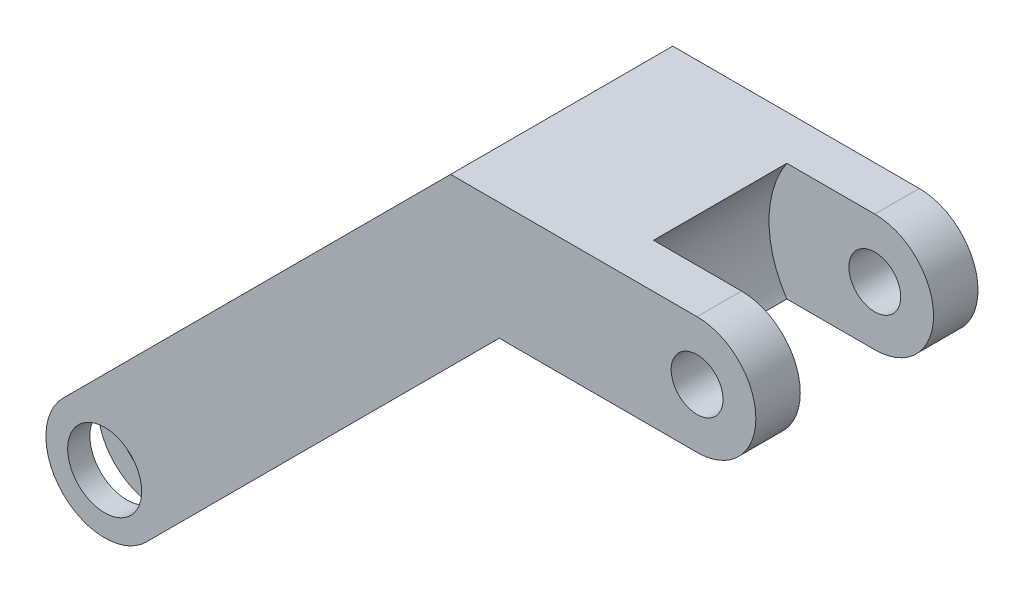
SolidWorks part; units mm, degrees
ref_plane "Alzado" through (0, 0, 0) normal (0, 0, 1) x (1, 0, 0)
ref_plane "Planta" through (0, 0, 0) normal (0, 1, 0) x (1, 0, 0)
ref_plane "Vista lateral" through (0, 0, 0) normal (1, 0, 0) x (0, 0, -1)
sketch "Croquis1" plane through (0, 0, 0) normal (0, 0, 1) x (1, 0, 0)
  line L0 (-2.8063, 2.8063) -> (23.3561, 28.9688)
  line L1 (23.3561, 28.9688) -> (40, 28.9688)
  line L2 (40, 28.9688) -> (40, 21.0312)
  line L3 (40, 21.0312) -> (26.6439, 21.0312)
  line L4 (26.6439, 21.0312) -> (2.8063, -2.8063)
  line L5 (0, -3.9687) -> (16.1518, -3.9687) construction
  line L6 (0, 0) -> (0, 22.779) construction
  line L7 (18.0887, 25) -> (31.0225, 25) construction
  line L8 (-11.9933, 0) -> (35.7455, 0) construction
  circle A0 centre (0, 0) radius 3.9687
  circle A1 centre (40, 25) radius 3.9687
  dimension "D1" = 7.9375
  dimension "D3" = 40
  dimension "D2" = 45
  dimension "D4" = 25
extrude "Saliente-Extruir1" add sketch "Croquis1" along normal mid plane 15 contours A0 | A1 L1 L0 A0 L4 L3 | L2 A1 | L2 A1 region at (18.2367, 16.7569, 0) region at (0, 0, 0) region at (41.6844, 25, 0) region at (38.3156, 25, 0)
sketch "Croquis2" plane through (-2.8063, 2.8063, 0) normal (-0.7071, 0.7071, 0) x (0, 0, 1)
  line L0 (0, 3.5718) -> (0, -6.6545) construction
  line L1 (-7.5, 0) -> (7.5, 0) construction
  line L2 (-7.5, 0) -> (-7.5, -3.9688) construction
  line L3 (-7.5, -3.9688) -> (7.5, -3.9688) construction
  line L4 (7.5, 0) -> (7.5, -3.9688) construction
  line L5 (-6, 0) -> (-4, 0)
  line L6 (-6, 0) -> (-6, -3.9688)
  line L7 (-6, -3.9688) -> (-4, -3.9688)
  line L8 (-4, 0) -> (-4, -3.9688)
  line L9 (6, -3.9687) -> (4, -3.9687)
  line L10 (4, 0) -> (4, -3.9687)
  line L11 (6, 0) -> (4, 0)
  line L12 (6, 0) -> (6, -3.9687)
  dimension "D1" = 2
  dimension "D2" = 3
extrude "Cortar-Extruir1" cut sketch "Croquis2" against normal blind 15
sketch "Croquis4" plane through (0, 0, 7.5) normal (0, 0, 1) x (1, 0, 0)
  circle A0 centre (0, 0) radius 2.5
  dimension "D1" = 5
extrude "Cortar-Extruir2" cut sketch "Croquis4" against normal blind 15
sketch "Croquis5" plane through (0, 0, 0) normal (0, 0, 1) x (1, 0, 0)
  circle A0 centre (40, 25) radius 7.1437
  dimension "D1" = 14.2875
extrude "Cortar-Extruir3" cut sketch "Croquis5" against normal mid plane 9
sketch "Croquis13" plane through (0, 0, 7.5) normal (0, 0, 1) x (1, 0, 0)
  circle A0 centre (40, 25) radius 1.75
  dimension "D1" = 3.5
extrude "Cortar-Extruir8" cut sketch "Croquis13" against normal through all
sketch "Croquis10" plane through (0, 0, 0) normal (0, 0, 1) x (1, 0, 0)
  line L0 (26.6439, 21.0312) -> (2.8063, -2.8063) construction
  line L1 (0, -1.4165) -> (0, 9.0296) construction
  circle A0 centre (17.5, 11.8873) radius 4
  circle A1 centre (17.5, 11.8873) radius 2
  dimension "D1" = 8
  dimension "D2" = 17.5
  dimension "D3" = 2
extrude "Cortar-Extruir7" cut sketch "Croquis10" against normal mid plane 3
sketch "Croquis12" plane through (0, 0, 0) normal (0, 0, 1) x (1, 0, 0)
  line L0 (33.322, 21.0312) -> (22.6439, 17.0312)
  line L1 (40, 21.0312) -> (26.6439, 21.0312) construction
  line L2 (26.6439, 21.0312) -> (2.8063, -2.8063) construction
  dimension "D1" = 4
rib "Nervio1" sketch "Croquis12" sketch "Croquis12" thickness 3 extrusion direction parallel to sketch draft on no parameters "D1"=3
